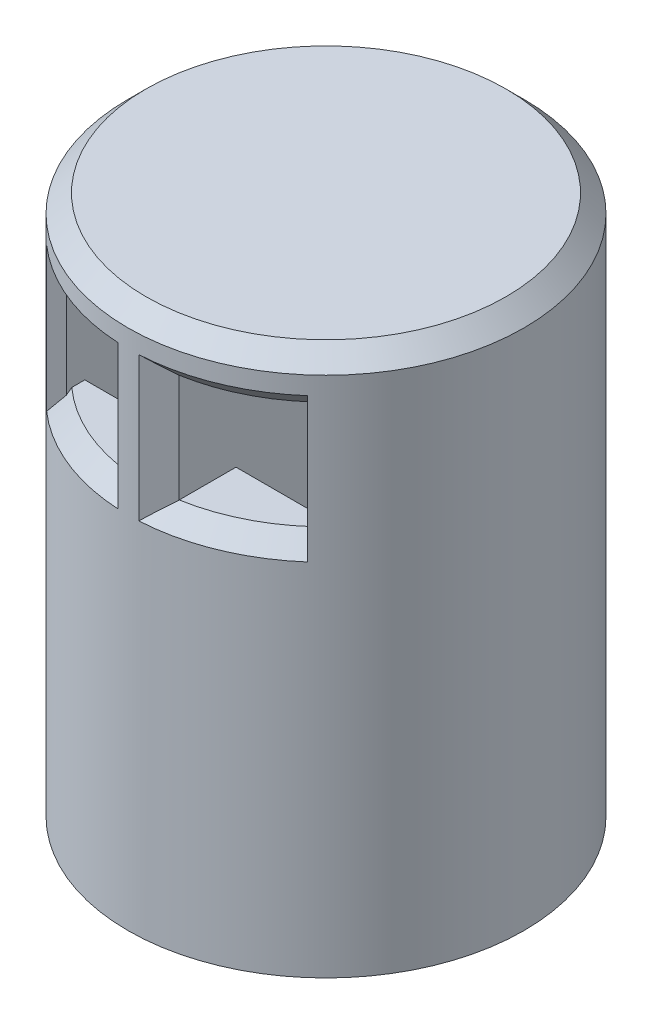
SolidWorks part; units mm, degrees
ref_plane "Front Plane" through (0, 0, 0) normal (0, 0, 1) x (1, 0, 0)
ref_plane "Top Plane" through (0, 0, 0) normal (0, 1, 0) x (1, 0, 0)
ref_plane "Right Plane" through (0, 0, 0) normal (1, 0, 0) x (0, 0, -1)
sketch "Sketch1" plane through (0, 0, 0) normal (0, 1, 0) x (1, 0, 0)
  circle A0 centre (0, 0) radius 5.5
  dimension "D1" = 11
extrude "Boss-Extrude1" add sketch "Sketch1" along normal blind 15
sketch "Sketch2" plane through (0, 0, 0) normal (0, -1, 0) x (1, 0, 0)
  line L1 (-3.35, 3.35) -> (3.35, 3.35)
  line L2 (-3.35, 3.35) -> (-3.35, -3.35)
  line L3 (-3.35, -3.35) -> (3.35, -3.35)
  line L4 (3.35, 3.35) -> (3.35, -3.35)
  line L5 (-3.35, 3.35) -> (3.35, -3.35) construction
  line L6 (-3.35, -3.35) -> (3.35, 3.35) construction
  point P0 (0, 0)
  dimension "D1" = 6.7
  dimension "D2" = 6.7
extrude "Cut-Extrude1" cut sketch "Sketch2" against normal blind 3.5
sketch "Sketch3" plane through (0, 3.5, 0) normal (0, -1, 0) x (1, 0, 0)
  line L0 (-3.35, -3.35) -> (3.35, -3.35) construction
  line L1 (-3.35, 3.35) -> (-0.85, 3.35)
  line L2 (-3.35, 3.35) -> (-3.35, -3.35)
  line L3 (-3.35, -3.35) -> (-0.85, -3.35)
  line L4 (-0.85, 3.35) -> (-0.85, -3.35)
  line L6 (0.85, -3.35) -> (3.35, -3.35)
  line L7 (0.85, -3.35) -> (0.85, 3.35)
  line L8 (0.85, 3.35) -> (3.35, 3.35)
  line L9 (3.35, -3.35) -> (3.35, 3.35)
  dimension "D1" = 2.5
  dimension "D2" = 2.5
extrude "Cut-Extrude2" cut sketch "Sketch3" against normal blind 10
sketch "Sketch4" plane through (0, 0, 3.35) normal (0, 0, -1) x (-1, 0, 0)
  line L0 (0.85, 13.5) -> (0.85, 3.5) construction
  line L1 (3.35, 13.5) -> (0.85, 13.5)
  line L2 (3.35, 13.5) -> (3.35, 10.5)
  line L3 (3.35, 10.5) -> (0.85, 10.5)
  line L4 (0.85, 13.5) -> (0.85, 10.5)
  line L5 (-0.85, 13.5) -> (-0.85, 3.5) construction
  line L6 (-3.35, 13.5) -> (-0.85, 13.5)
  line L7 (-3.35, 13.5) -> (-3.35, 10.5)
  line L8 (-3.35, 10.5) -> (-0.85, 10.5)
  line L9 (-0.85, 13.5) -> (-0.85, 10.5)
  dimension "D1" = 3
  dimension "D2" = 3
extrude "Cut-Extrude3" cut sketch "Sketch4" against normal through all
chamfer "Chamfer1" distance 0.5 angle 45 14 edges at (-0.85, 3.5, 0) (0.85, 3.5, 0) (-2.1673, 13.5, 5.055) (-3.35, 12, 4.3621) (-2.1673, 10.5, 5.055) (-0.85, 12, 5.4339) (2.1673, 13.5, 5.055) (0.85, 12, 5.4339) (3.35, 12, 4.3621) (2.1673, 10.5, 5.055) (0, 0, -3.35) (3.35, 0, 0) (0, 0, 3.35) (-3.35, 0, 0)
chamfer "Chamfer2" distance 0.5 angle 45 1 edges at (0, 15, 5.5)
